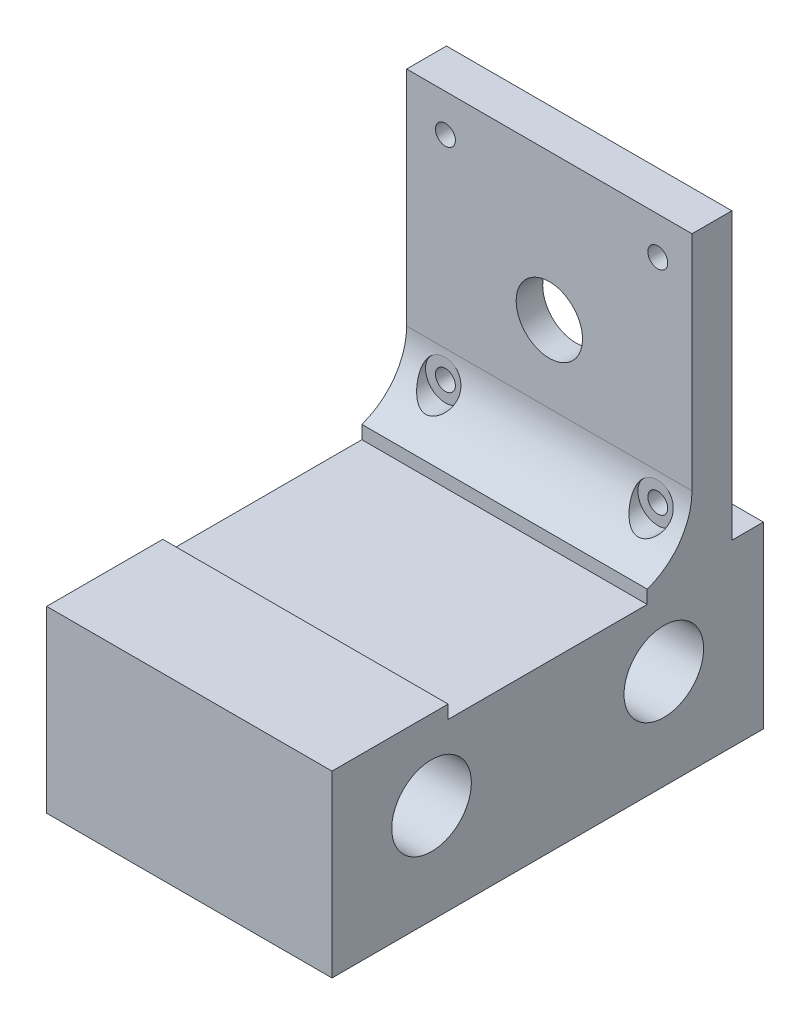
SolidWorks part; units mm, degrees
ref_plane "Front Plane" through (0, 0, 0) normal (0, 0, 1) x (1, 0, 0)
ref_plane "Top Plane" through (0, 0, 0) normal (0, 1, 0) x (1, 0, 0)
ref_plane "Right Plane" through (0, 0, 0) normal (1, 0, 0) x (0, 0, -1)
sketch "Sketch9" plane through (0, 0, 0) normal (0, 0, 1) x (1, 0, 0)
  line L0 (0, 0) -> (0, 27) construction
  line L1 (21.5, 27) -> (-21.5, 27)
  line L2 (-21.5, 27) -> (-21.5, 0)
  line L3 (-21.5, 0) -> (21.5, 0)
  line L4 (21.5, 27) -> (21.5, 0)
  dimension "D1" = 43
  dimension "D2" = 27
extrude "Boss-Extrude1" add sketch "Sketch9" along normal mid plane 65
sketch "Sketch10" plane through (21.5, 0, 0) normal (1, 0, 0) x (0, 0, -1)
  line L0 (0, 27) -> (0, 0) construction
  line L1 (-32.5, 27) -> (32.5, 27) construction
  line L2 (-32.5, 0) -> (32.5, 0) construction
  circle A0 centre (-17.5, 15) radius 6
  circle A1 centre (17.5, 15) radius 6
  dimension "D1" = 12
  dimension "D2" = 35
  dimension "D3" = 15
extrude "Cut-Extrude1" cut sketch "Sketch10" against normal through all both and the other way through all
sketch "Sketch11" plane through (0, 0, 0) normal (0, -1, 0) x (1, 0, 0)
  line L0 (0, 32.5) -> (0, -32.5) construction
  line L1 (-21.5, 32.5) -> (21.5, 32.5) construction
  line L2 (-21.5, -32.5) -> (21.5, -32.5) construction
  line L3 (21.5, 0) -> (-21.5, 0) construction
  line L4 (21.5, 32.5) -> (21.5, -32.5) construction
  line L5 (-21.5, 32.5) -> (-21.5, -32.5) construction
  line L6 (12, -12) -> (13.5, -9.4019)
  line L7 (13.5, 9.4019) -> (16.5, 9.4019)
  line L8 (16.5, 9.4019) -> (18, 12)
  line L9 (18, 12) -> (16.5, 14.5981)
  line L10 (16.5, 14.5981) -> (13.5, 14.5981)
  line L11 (13.5, 14.5981) -> (12, 12)
  line L12 (12, 12) -> (13.5, 9.4019)
  line L13 (13.5, -14.5981) -> (12, -12)
  line L14 (16.5, -14.5981) -> (13.5, -14.5981)
  line L15 (18, -12) -> (16.5, -14.5981)
  line L16 (16.5, -9.4019) -> (18, -12)
  line L17 (13.5, -9.4019) -> (16.5, -9.4019)
  line L18 (-13.5, -9.4019) -> (-16.5, -9.4019)
  line L19 (-16.5, -9.4019) -> (-18, -12)
  line L20 (-18, -12) -> (-16.5, -14.5981)
  line L21 (-16.5, -14.5981) -> (-13.5, -14.5981)
  line L22 (-13.5, -14.5981) -> (-12, -12)
  line L23 (-12, -12) -> (-13.5, -9.4019)
  line L24 (-12, 12) -> (-13.5, 9.4019)
  line L25 (-13.5, 14.5981) -> (-12, 12)
  line L26 (-16.5, 14.5981) -> (-13.5, 14.5981)
  line L27 (-18, 12) -> (-16.5, 14.5981)
  line L28 (-16.5, 9.4019) -> (-18, 12)
  line L29 (-13.5, 9.4019) -> (-16.5, 9.4019)
  circle A0 centre (15, 12) radius 2.5981 construction
  circle A1 centre (15, -12) radius 2.5981 construction
  circle A2 centre (-15, -12) radius 2.5981 construction
  circle A3 centre (-15, 12) radius 2.5981 construction
  dimension "D1" = 3
  dimension "D2" = 24
  dimension "D3" = 30
extrude "Cut-Extrude2" cut sketch "Sketch11" against normal blind 3
sketch "Sketch14" plane through (21.5, 0, 0) normal (1, 0, 0) x (0, 0, -1)
  line L0 (0, 27) -> (0, 0) construction
  line L1 (-32.5, 27) -> (32.5, 27) construction
  line L2 (-32.5, 0) -> (32.5, 0) construction
  line L3 (-15, 27) -> (-15, 25)
  line L4 (-15, 25) -> (15, 25)
  line L5 (15, 27) -> (15, 25)
  line L6 (-15, 27) -> (15, 27)
  point P10 (0, 25)
  dimension "D1" = 30
  dimension "D2" = 2
extrude "Cut-Extrude4" cut sketch "Sketch14" against normal through all both and the other way through all
sketch "Sketch15" plane through (0, 27, 0) normal (0, 1, 0) x (1, 0, 0)
  line L7 (-21.5, 27.75) -> (21.5, 27.75)
  line L8 (-21.5, 15) -> (-21.5, 32.5) construction
  line L9 (21.5, 15) -> (21.5, 32.5) construction
  line L10 (21.5, 21.75) -> (-21.5, 21.75)
  line L11 (-21.5, 21.75) -> (-21.5, 27.75)
  line L12 (21.5, 32.5) -> (-21.5, 32.5) construction
  line L13 (21.5, 21.75) -> (21.5, 27.75)
  dimension "D3" = 4.75
  dimension "D4" = 6
extrude "Boss-Extrude2" add sketch "Sketch15" along normal blind 43
hole_wizard "Ø3.0mm Dowel Hole1" positions "3DSketch3" profile "Sketch19" hole size "Ø3.0" standard "ISO"
sketch3d "3DSketch3"
  line L3 (-13.5, 0, -14.5981) -> (-16.5, 0, -9.4019) construction
  line L5 (16.5, 0, -14.5981) -> (13.5, 0, -9.4019) construction
  line L7 (16.5, 0, 9.4019) -> (13.5, 0, 14.5981) construction
  line L9 (-16.5, 0, 14.5981) -> (-13.5, 0, 9.4019) construction
  point P27 (-15, 0, 12)
  point P29 (-15, 0, -12)
  point P31 (15, 0, -12)
  point P33 (15, 0, 12)
sketch "Sketch19" plane through (15, 0, 12) normal (1, 0, 0) x (0, 0, -1)
  line L0 (0, 0) -> (0, 6.9013)
  line L1 (0, 6.9013) -> (1.5, 6)
  line L2 (1.5, 6) -> (1.5, 0)
  line L5 (1.5, 0) -> (0, 0)
  line L10 (0, 6.9013) -> (-1.5, 6) construction
  line L11 (0, -6.35) -> (0, 107.95) construction
  dimension "Hole Dia." = 3
  dimension "Hole Depth" = 6
  dimension "Drill Angle" = 118
fillet "Fillet2" radius 10 1 edges at (0, 27, -21.75)
sketch "Sketch20" plane through (0, 0, -27.75) normal (0, 0, -1) x (-1, 0, 0)
  line L2 (-21.5, 27) -> (21.5, 27) construction
  line L3 (-21.5, 48) -> (21.5, 48) construction
  line L4 (-21.5, 70) -> (-21.5, 27) construction
  line L5 (21.5, 70) -> (21.5, 27) construction
  circle A0 centre (0, 48) radius 11
  dimension "D2" = 22
  dimension "D1" = 21
extrude "Cut-Extrude5" cut sketch "Sketch20" against normal blind 2
sketch "Sketch21" plane through (0, 0, -27.75) normal (0, 0, -1) x (-1, 0, 0)
  line L0 (0, 48) -> (-16.3418, 64.3418) construction
  line L1 (0, 48) -> (0, 30.7275) construction
  circle A0 centre (0, 48) radius 5
  circle A1 centre (-16.3418, 64.3418) radius 1.5
  circle A2 centre (15.6582, 64.3418) radius 1.5
  circle A3 centre (15.6582, 32.3418) radius 1.5
  circle A4 centre (-16.3418, 32.3418) radius 1.5
  point P14 (-0.3418, 48.3418)
  dimension "D1" = 10
  dimension "D3" = 32
  dimension "D4" = 3
  dimension "D5" = 135
  dimension "D2" = 4
extrude "Cut-Extrude6" cut sketch "Sketch21" against normal through all both and the other way through all
sketch "Sketch23" plane through (0, 0, -21.75) normal (0, 0, 1) x (1, 0, 0)
  circle A0 centre (-15.6582, 32.3418) radius 3
  circle A1 centre (16.3418, 32.3418) radius 3
  dimension "D1" = 6
  dimension "D2" = 6
extrude "Cut-Extrude7" cut sketch "Sketch23" along normal blind 6
